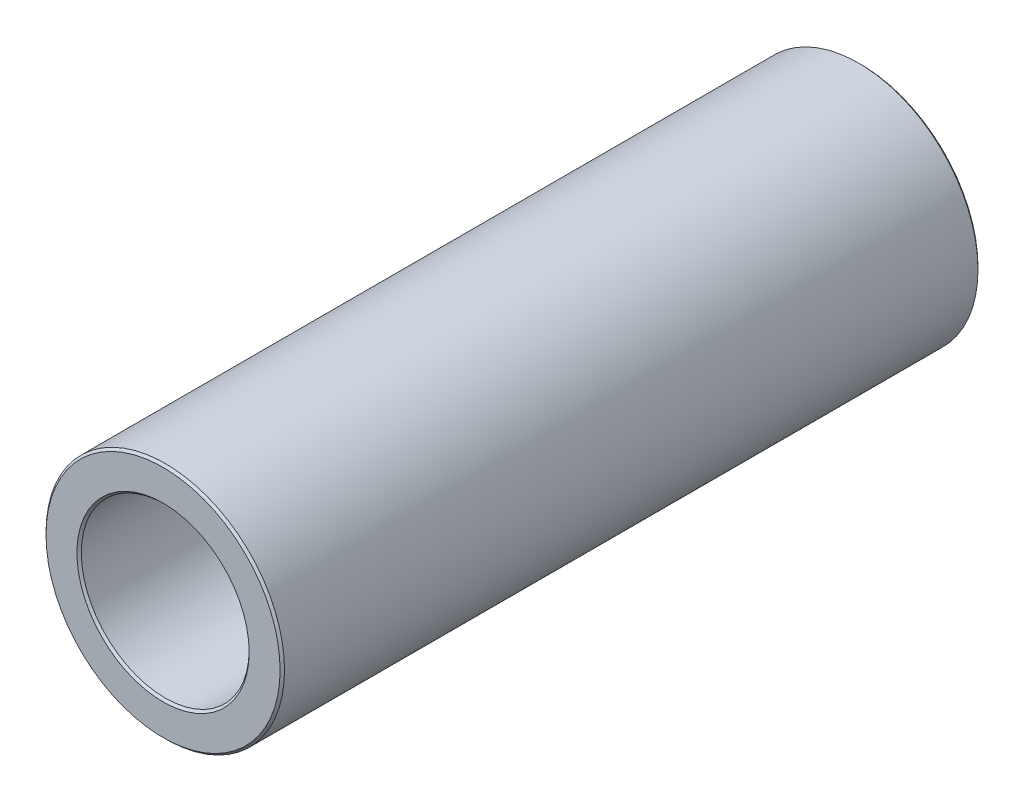
SolidWorks part; units mm, degrees
material "1.0037 (S235JR)"
ref_plane "E_Rechts" through (0, 0, 0) normal (0, 0, 1) x (1, 0, 0)
ref_plane "E_Oben" through (0, 0, 0) normal (0, 1, 0) x (1, 0, 0)
ref_plane "E_Vorne" through (0, 0, 0) normal (1, 0, 0) x (0, 0, -1)
ref_axis "A_Drehachse" through (0, 0, 55) along (0, 0, -1)
sketch "Skizze1" plane through (0, 0, 0) normal (0, 0, 1) x (1, 0, 0)
  circle A0 centre (0, 0) radius 27
  circle A1 centre (0, 0) radius 19
  dimension "D1" = 54
  dimension "D2" = 38
extrude "Aufsatz-Linear austragen1" add sketch "Skizze1" along normal mid plane 158
chamfer "Fase1" distance 0.5 angle 45 4 edges at (27, 0, -79) (27, 0, 79) (19, 0, -79) (19, 0, 79)
